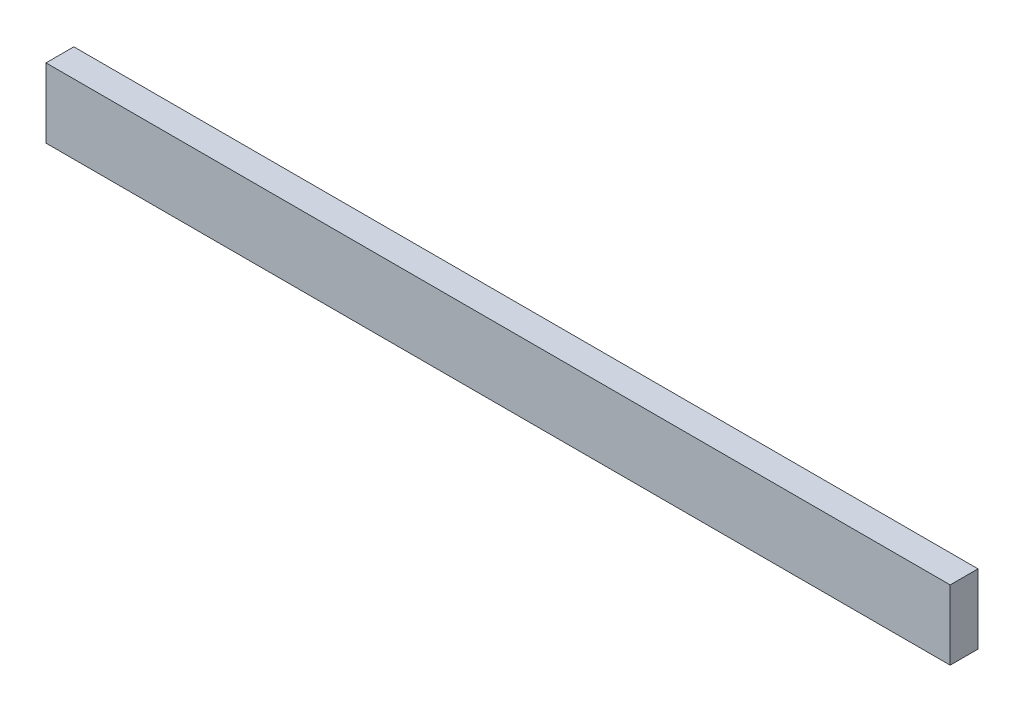
SolidWorks part; units mm, degrees
ref_plane "Plano frontal" through (0, 0, 0) normal (0, 0, 1) x (1, 0, 0)
ref_plane "Plano superior" through (0, 0, 0) normal (0, 1, 0) x (1, 0, 0)
ref_plane "Plano direito" through (0, 0, 0) normal (1, 0, 0) x (0, 0, -1)
sketch "Esboço1" plane through (0, 0, 0) normal (0, 0, 1) x (1, 0, 0)
  line L1 (-72.1079, 0) -> (57.8921, 0)
  line L2 (-72.1079, 0) -> (-72.1079, -10)
  line L3 (-72.1079, -10) -> (57.8921, -10)
  line L4 (57.8921, 0) -> (57.8921, -10)
  dimension "D1" = 130
  dimension "D2" = 10
extrude "Ressalto-extrusão2" add sketch "Esboço1" along normal blind 4
